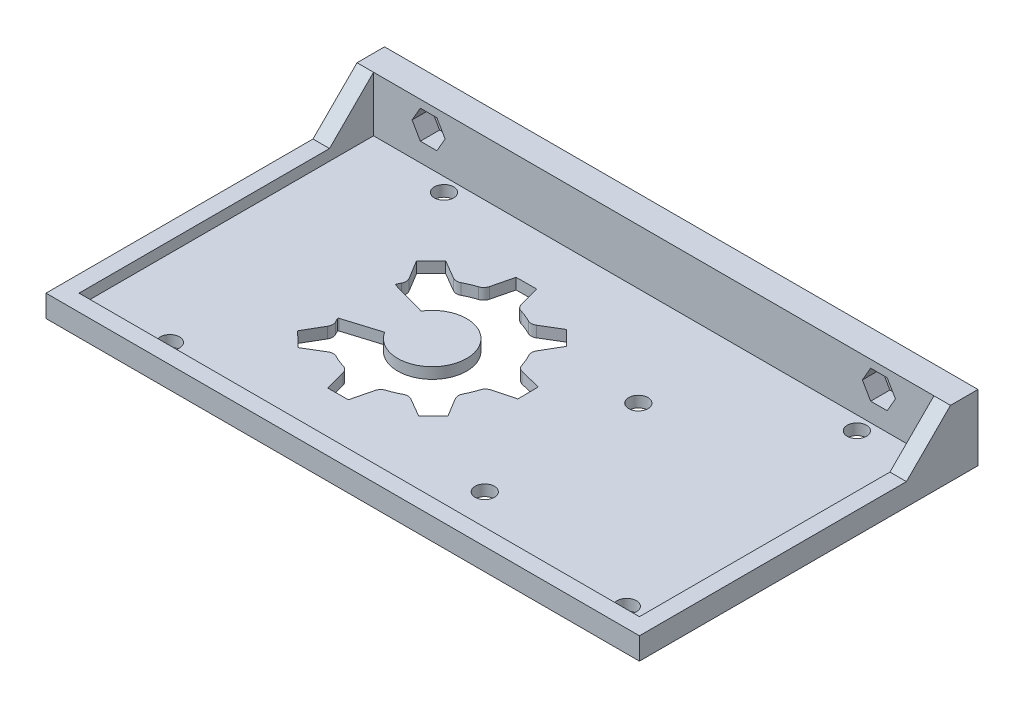
SolidWorks part; units mm, degrees
ref_plane "Front Plane" through (0, 0, 0) normal (0, 0, 1) x (1, 0, 0)
ref_plane "Top Plane" through (0, 0, 0) normal (0, 1, 0) x (1, 0, 0)
ref_plane "Right Plane" through (0, 0, 0) normal (1, 0, 0) x (0, 0, -1)
sketch "Sketch1" plane through (0, 0, 0) normal (0, 1, 0) x (1, 0, 0)
  line L0 (0, 0) -> (0, 53.5)
  line L1 (0, 53.5) -> (101.8, 53.5)
  line L2 (101.8, 53.5) -> (101.8, 0)
  line L3 (101.8, 0) -> (0, 0)
  line L4 (-3, 56.5) -> (104.8, 56.5)
  line L5 (104.8, 56.5) -> (104.8, -3)
  line L6 (104.8, -3) -> (-3, -3)
  line L7 (-3, -3) -> (-3, 56.5)
  line L8 (23.5948, 37.7055) -> (26.2216, 40.3769)
  line L33 (35.2002, 44.1847) -> (38.9466, 44.2162)
  line L34 (47.9879, 40.5599) -> (50.6592, 37.9331)
  line L35 (54.4671, 28.9545) -> (54.4986, 25.2082)
  line L36 (50.8423, 16.1668) -> (48.2155, 13.4955)
  line L37 (25.5551, 21.6457) -> (31.9041, 23.6071)
  line L38 (23.5948, 37.7055) -> (25.6584, 34.2931)
  line L39 (39.2369, 9.6877) -> (35.4906, 9.6562)
  line L40 (26.4492, 13.3125) -> (23.7779, 15.9392)
  line L41 (26.2216, 40.3769) -> (29.6683, 38.371)
  line L42 (35.2002, 44.1847) -> (34.2464, 40.3126)
  line L43 (38.9466, 44.2162) -> (39.9653, 40.3606)
  line L44 (47.9879, 40.5599) -> (44.5755, 38.4963)
  line L45 (50.6592, 37.9331) -> (48.6534, 34.4864)
  line L46 (54.4671, 28.9545) -> (50.5949, 29.9083)
  line L47 (54.4986, 25.2082) -> (50.643, 24.1894)
  line L48 (50.8423, 16.1668) -> (48.7787, 19.5793)
  line L49 (48.2155, 13.4955) -> (44.7688, 15.5014)
  line L50 (39.2369, 9.6877) -> (40.1907, 13.5598)
  line L51 (35.4906, 9.6562) -> (34.4718, 13.5117)
  line L52 (26.4492, 13.3125) -> (29.8617, 15.376)
  line L53 (23.7779, 15.9392) -> (25.7838, 19.3859)
  line L54 (31.8893, 30.2415) -> (25.4683, 32.0271)
  line L55 (14, 52.4633) -> (14, 2.5) construction
  circle A0 centre (15.3, 51) radius 1.75
  circle A1 centre (14, 2.5) radius 1.75
  circle A2 centre (90.3, 51) radius 1.75
  circle A3 centre (97, 2.5) radius 1.75
  circle A4 centre (66.1, 35.5) radius 1.75
  circle A5 centre (66.1, 7.6) radius 1.75
  arc A6 (41.1519, 14.5875) -> (43.3619, 15.5247) centre (37.2186, 26.9362) ccw
  arc A7 (25.4726, 21.4595) -> (25.8071, 20.7928) centre (37.2186, 26.9362) ccw
  arc A8 (25.5551, 21.6457) -> (25.4726, 21.4595) centre (25.595, 21.5166) ccw
  arc A9 (25.3811, 32.2123) -> (25.4683, 32.0271) centre (25.5045, 32.1573) ccw
  arc A10 (31.0752, 38.3476) -> (29.6683, 38.371) centre (30.3926, 39.6155) cw
  arc A11 (25.7054, 32.8868) -> (25.6584, 34.2931) centre (24.4262, 33.5479) ccw
  arc A12 (40.9436, 39.3493) -> (39.9653, 40.3606) centre (41.3575, 40.7285) cw
  arc A13 (33.2852, 39.2849) -> (34.2464, 40.3126) centre (32.8482, 40.657) ccw
  arc A14 (48.63, 33.0795) -> (48.6534, 34.4864) centre (49.8979, 33.7621) cw
  arc A15 (43.1691, 38.4493) -> (44.5755, 38.4963) centre (43.8303, 39.7285) ccw
  arc A16 (49.6317, 23.2111) -> (50.643, 24.1894) centre (51.0109, 22.7972) cw
  arc A17 (49.5673, 30.8695) -> (50.5949, 29.9083) centre (50.9393, 31.3065) ccw
  arc A18 (43.3619, 15.5247) -> (44.7688, 15.5014) centre (44.0445, 14.2568) cw
  arc A19 (48.7317, 20.9856) -> (48.7787, 19.5793) centre (50.0109, 20.3244) ccw
  arc A20 (33.4935, 14.5231) -> (34.4718, 13.5117) centre (33.0796, 13.1438) cw
  arc A21 (41.1519, 14.5875) -> (40.1907, 13.5598) centre (41.5889, 13.2154) ccw
  arc A22 (25.8071, 20.7928) -> (25.7838, 19.3859) centre (24.5392, 20.1102) cw
  arc A23 (31.268, 15.423) -> (29.8617, 15.376) centre (30.6068, 14.1438) ccw
  arc A24 (31.268, 15.423) -> (33.4935, 14.5231) centre (37.2186, 26.9362) ccw
  arc A25 (25.7054, 32.8868) -> (25.3811, 32.2123) centre (37.2186, 26.9362) ccw
  arc A26 (33.2852, 39.2849) -> (31.0752, 38.3476) centre (37.2186, 26.9362) ccw
  arc A27 (43.1691, 38.4493) -> (40.9436, 39.3493) centre (37.2186, 26.9362) ccw
  arc A28 (49.5673, 30.8695) -> (48.63, 33.0795) centre (37.2186, 26.9362) ccw
  arc A29 (48.7317, 20.9856) -> (49.6317, 23.2111) centre (37.2186, 26.9362) ccw
  arc A30 (31.9041, 23.6071) -> (31.8893, 30.2415) centre (37.2186, 26.9362) ccw
  point P89 (37.0957, 26.9356)
  dimension "D3" = 3.5
  dimension "D13" = 0.1351
  dimension "D14" = 0.1351
  dimension "D1" = 53.5
  dimension "D2" = 101.8
  dimension "D4" = 14
  dimension "D5" = 75
  dimension "D6" = 4.8
  dimension "D7" = 2.5
  dimension "D8" = 2.5
  dimension "D9" = 27.9
  dimension "D10" = 5.1
  dimension "D11" = 50.8
  dimension "D15" = 1.3
  dimension "D12" = 3
extrude "Boss-Extrude1" add sketch "Sketch1" along normal blind 2 contours A30 L37 A8 A7 A22 L53 L40 L52 A23 A24 A20 L51 L39 L50 A21 A6 A18 L49 L36 L48 A19 A29 A16 L47 L35 L46 A17 A28 A14 L45 L34 L44 A15 A27 A12 L43 L33 L42 A13 A26 A10 L41 L8 L38 A11 A25 A9 L54 | L4 L5 L6 L7 | A0 | A1 | A4 | A5 | A2 | A3 region at (25.2388, 0, -38.7161)
extrude "Boss-Extrude2" add sketch "Sketch1<3>" along normal blind 2 from surface contours L7 L6 L5 L4 L2 L3 L0 L1 | L55 L4 L7 L6 L3 L0 L1 region at (50.9, 0, -55.2687) region at (13.8179, 0, -51) body kept at (104.8, 4, 3) starting at face at (38.0477, 2, -26.9429)
sketch "Sketch1<3>" plane through (0, 0, 0) normal (0, 1, 0) x (1, 0, 0) same geometry as "Sketch1"
sketch "Sketch3" plane through (0, 0, 0) normal (0, -1, 0) x (1, 0, 0)
  line L0 (-3, 3) -> (-3, -56.5) construction
  line L1 (104.8, -58.5) -> (-3, -58.5)
  line L2 (104.8, -58.5) -> (104.8, -53.5)
  line L3 (104.8, -53.5) -> (-3, -53.5)
  line L4 (-3, -58.5) -> (-3, -53.5)
  line L5 (0, -53.5) -> (101.8, -53.5) construction
  line L6 (104.8, -56.5) -> (104.8, 3) construction
  dimension "D1" = 5
extrude "Boss-Extrude3" add sketch "Sketch3" against normal blind 12
chamfer "Chamfer1" distance 8 angle 45 2 edges at (-1.5, 4, -53.5) (103.3, 4, -53.5)
sketch "Sketch4" plane through (0, 0, -53.5) normal (0, 0, 1) x (1, 0, 0)
  line L0 (-3, 4) -> (-3, 12) construction
  line L7 (0, 12) -> (0, 2) construction
  line L8 (11.5, 10.5981) -> (8.5, 10.5981)
  line L9 (8.5, 10.5981) -> (7, 8)
  line L10 (7, 8) -> (8.5, 5.4019)
  line L11 (8.5, 5.4019) -> (11.5, 5.4019)
  line L12 (11.5, 5.4019) -> (13, 8)
  line L13 (13, 8) -> (11.5, 10.5981)
  line L15 (50.9, 40.6866) -> (50.9, -6.6536) construction
  line L16 (101.8, 12) -> (0, 12) construction
  line L17 (90.3, 10.5981) -> (93.3, 10.5981)
  line L18 (88.8, 8) -> (90.3, 10.5981)
  line L19 (90.3, 5.4019) -> (88.8, 8)
  line L20 (93.3, 5.4019) -> (90.3, 5.4019)
  line L21 (94.8, 8) -> (93.3, 5.4019)
  line L22 (93.3, 10.5981) -> (94.8, 8)
  circle A0 centre (10, 8) radius 3 construction
  circle A1 centre (10, 8) radius 1.75
  circle A2 centre (91.8, 8) radius 3 construction
  circle A3 centre (91.8, 8) radius 1.75
  point P10 (-3, 8)
  point P18 (50.9, 12)
  dimension "D1" = 6
  dimension "D3" = 3.5
  dimension "D2" = 10
extrude "Cut-Extrude1" cut sketch "Sketch4" against normal blind 3.5 contours L8 L9 L10 L11 L12 L13 | L17 L22 L21 L20 L19 L18
extrude "Cut-Extrude3" cut sketch "Sketch4<4>" against normal through all contours A1 | A3
sketch "Sketch4<4>" plane through (0, 0, -53.5) normal (0, 0, 1) x (1, 0, 0) same geometry as "Sketch4"
